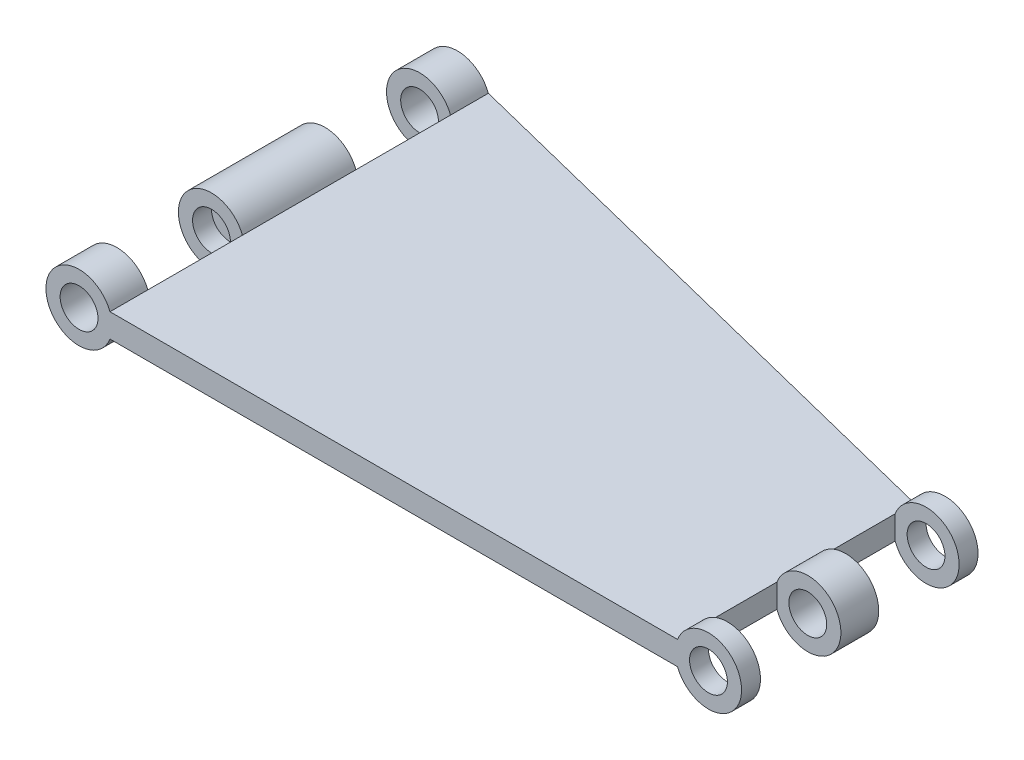
SolidWorks part; units mm, degrees
ref_plane "前视基准面" through (0, 0, 0) normal (0, 0, 1) x (1, 0, 0)
ref_plane "上视基准面" through (0, 0, 0) normal (0, 1, 0) x (1, 0, 0)
ref_plane "右视基准面" through (0, 0, 0) normal (1, 0, 0) x (0, 0, -1)
sketch "草图1" plane through (0, 0, 0) normal (0, 1, 0) x (1, 0, 0)
  line L0 (-79.4926, 46.9345) -> (-79.4926, -33.0655)
  line L1 (-79.4926, -33.0655) -> (40.5074, -33.0655)
  line L2 (40.5074, -33.0655) -> (40.5074, 16.9345)
  line L3 (40.5074, 16.9345) -> (-79.4926, 46.9345)
  dimension "D1" = 80
  dimension "D2" = 120
  dimension "D3" = 50
extrude "凸台-拉伸1" add sketch "草图1" along normal blind 5
sketch "草图3" plane through (0, 0, 33.0655) normal (0, 0, 1) x (1, 0, 0)
  circle A0 centre (-86.0309, 2.5) radius 7
  circle A1 centre (-86.0309, 2.5) radius 1.5
  dimension "D1" = 14
  dimension "D2" = 3
extrude "凸台-拉伸2" add sketch "草图3" against normal blind 80
sketch "草图4" plane through (0, 5, 0) normal (0, 1, 0) x (1, 0, 0)
  line L0 (-79.4926, 46.9345) -> (-79.4926, -33.0655) construction
  line L1 (-79.4926, 38.9345) -> (-93.0309, 38.9345)
  line L2 (-79.4926, 38.9345) -> (-79.4926, 18.9345)
  line L3 (-79.4926, 18.9345) -> (-93.0309, 18.9345)
  line L4 (-93.0309, 38.9345) -> (-93.0309, 18.9345)
  line L5 (-93.0309, 46.9345) -> (-93.0309, -33.0655) construction
  line L6 (-93.0309, -33.0655) -> (-79.4926, -33.0655) construction
  line L7 (-79.4926, -25.0655) -> (-93.0309, -25.0655)
  line L8 (-79.4926, -25.0655) -> (-79.4926, -5.0655)
  line L9 (-79.4926, -5.0655) -> (-93.0309, -5.0655)
  line L10 (-93.0309, -25.0655) -> (-93.0309, -5.0655)
  line L11 (-84.5309, 46.9345) -> (-87.5309, 46.9345) construction
  dimension "D1" = 8
  dimension "D2" = 20
  dimension "D3" = 8
  dimension "D4" = 20
extrude "切除-拉伸1" cut sketch "草图4" against normal blind 80 and the other way blind 80 contours L2 L1 L4 L3 | L8 L7 L10 L9
sketch "草图5" plane through (0, 0, 33.0655) normal (0, 0, 1) x (1, 0, 0)
  circle A0 centre (47.0457, 2.5) radius 7
  circle A1 centre (47.0457, 2.5) radius 4
  dimension "D1" = 14
  dimension "D2" = 8
extrude "凸台-拉伸3" add sketch "草图5" against normal blind 50
sketch "草图6" plane through (0, 5, 0) normal (0, 1, 0) x (1, 0, 0)
  line L0 (40.5074, -33.0655) -> (40.5074, 16.9345) construction
  line L1 (40.5074, 12.9345) -> (54.0457, 12.9345)
  line L2 (40.5074, 12.9345) -> (40.5074, -4.0655)
  line L3 (40.5074, -4.0655) -> (54.0457, -4.0655)
  line L4 (54.0457, 12.9345) -> (54.0457, -4.0655)
  line L5 (54.0457, -33.0655) -> (54.0457, 16.9345) construction
  line L6 (54.0457, 16.9345) -> (40.5074, 16.9345) construction
  line L7 (40.5074, -29.0655) -> (54.0457, -29.0655)
  line L8 (40.5074, -29.0655) -> (40.5074, -12.0655)
  line L9 (40.5074, -12.0655) -> (54.0457, -12.0655)
  line L10 (54.0457, -29.0655) -> (54.0457, -12.0655)
  line L11 (40.5074, -33.0655) -> (54.0457, -33.0655) construction
  dimension "D1" = 4
  dimension "D2" = 8
  dimension "D3" = 4
  dimension "D4" = 17
extrude "切除-拉伸2" cut sketch "草图6" against normal blind 50 and the other way blind 50
sketch "草图7" plane through (0, 0, 33.0655) normal (0, 0, 1) x (1, 0, 0)
  circle A0 centre (-86.0309, 2.5) radius 4
  dimension "D1" = 8
extrude "切除-拉伸3" cut sketch "草图7" against normal blind 32
sketch "草图8" plane through (0, 0, -46.9345) normal (0, 0, -1) x (-1, 0, 0)
  circle A0 centre (86.0309, 2.5) radius 4
  dimension "D1" = 8
extrude "切除-拉伸4" cut sketch "草图8" against normal blind 32
